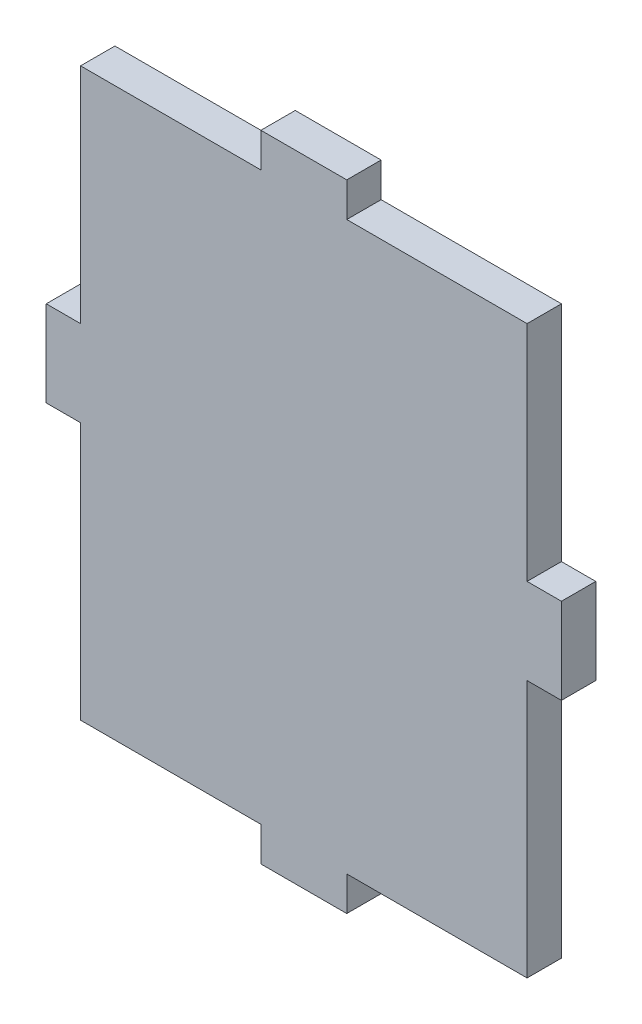
SolidWorks part; units mm, degrees
ref_plane "Front Plane" through (0, 0, 0) normal (0, 0, 1) x (1, 0, 0)
ref_plane "Top Plane" through (0, 0, 0) normal (0, 1, 0) x (1, 0, 0)
ref_plane "Right Plane" through (0, 0, 0) normal (1, 0, 0) x (0, 0, -1)
sketch "Sketch1" plane through (0, 0, 0) normal (0, 0, 1) x (1, 0, 0)
  line L1 (0, 0) -> (52, 0)
  line L2 (0, 0) -> (0, 66)
  line L3 (0, 66) -> (52, 66)
  line L4 (52, 0) -> (52, 66)
  dimension "D1" = 52
  dimension "D2" = 66
extrude "Boss-Extrude1" add sketch "Sketch1" along normal blind 4
sketch "Sketch2" plane through (0, 0, 4) normal (0, 0, 1) x (1, 0, 0)
  line L0 (0, 66) -> (0, 0) construction
  line L1 (0, 40) -> (-4, 40)
  line L2 (0, 40) -> (0, 30)
  line L3 (0, 30) -> (-4, 30)
  line L4 (-4, 40) -> (-4, 30)
  line L5 (52, 0) -> (52, 66) construction
  line L6 (52, 40) -> (56, 40)
  line L7 (52, 40) -> (52, 30)
  line L8 (52, 30) -> (56, 30)
  line L9 (56, 40) -> (56, 30)
  line L10 (0, 0) -> (52, 0) construction
  line L11 (21, 0) -> (31, 0)
  line L12 (21, 0) -> (21, -4)
  line L13 (21, -4) -> (31, -4)
  line L14 (31, 0) -> (31, -4)
  line L15 (52, 66) -> (0, 66) construction
  line L16 (21, 66) -> (31, 66)
  line L17 (21, 66) -> (21, 70)
  line L18 (21, 70) -> (31, 70)
  line L19 (31, 66) -> (31, 70)
  line L21 (26, 0) -> (26, 23.7889) construction
  dimension "D1" = 10
  dimension "D2" = 10
  dimension "D3" = 26
  dimension "D4" = 10
  dimension "D6" = 4
extrude "Boss-Extrude2" add sketch "Sketch2" against normal blind 4
